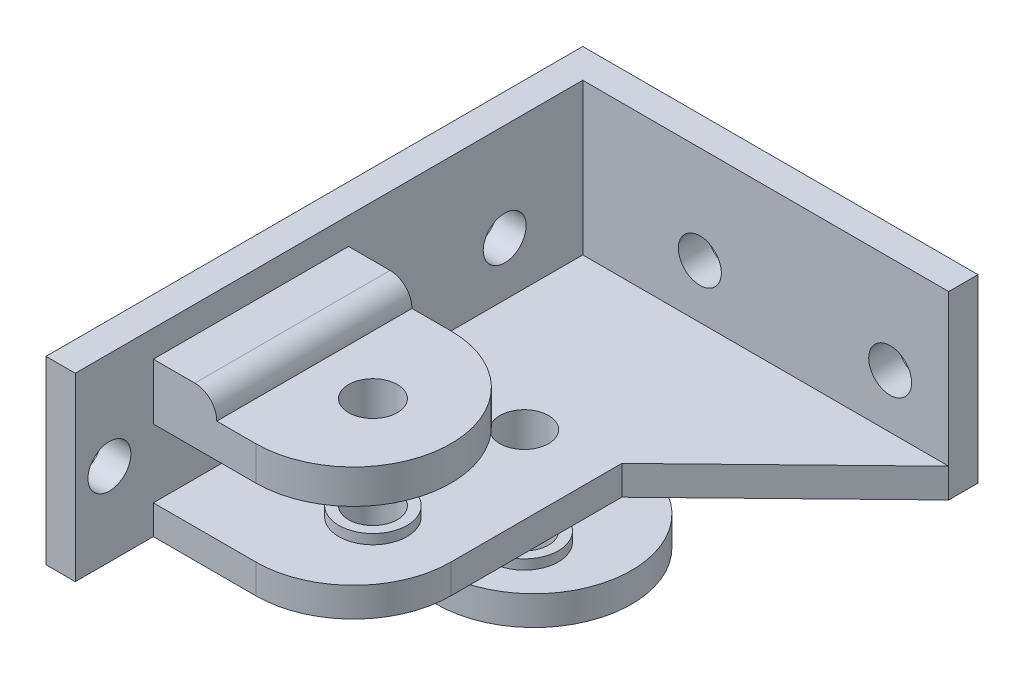
SolidWorks part; units mm, degrees
material "ABS"
ref_plane "Front Plane" through (0, 0, 0) normal (0, 0, 1) x (1, 0, 0)
ref_plane "Top Plane" through (0, 0, 0) normal (0, 1, 0) x (1, 0, 0)
ref_plane "Right Plane" through (0, 0, 0) normal (1, 0, 0) x (0, 0, -1)
sketch "Sketch1" plane through (0, 0, 0) normal (0, 1, 0) x (1, 0, 0)
  line L0 (40.5, 0) -> (0, 0)
  line L1 (0, 0) -> (0, -55)
  line L2 (0, -55) -> (3, -55)
  line L3 (3, -55) -> (3, -3)
  line L4 (3, -3) -> (40.5, -3)
  line L5 (40.5, -3) -> (40.5, 0)
  dimension "D1" = 3
  dimension "D2" = 40.5
  dimension "D3" = 55
extrude "Boss-Extrude1" add sketch "Sketch1" along normal blind 18.5
sketch "Sketch2" plane through (0, 0, 0) normal (0, -1, 0) x (1, 0, 0)
  line L0 (40.5, 3) -> (23.5, 19.5)
  line L1 (23.5, 19.5) -> (23.5, 37)
  line L2 (13.5, 47) -> (3, 47)
  line L3 (3, 3) -> (3, 55) construction
  line L4 (3, 47) -> (3, 3)
  line L5 (3, 3) -> (40.5, 3)
  line L7 (3, 55) -> (0, 55) construction
  line L8 (40.5, 0) -> (0, 0) construction
  arc A0 (13.5, 47) -> (23.5, 37) centre (13.5, 37) cw
  dimension "D3" = 19.5
  dimension "D1" = 10
  dimension "D2" = 17
  dimension "D4" = 8
extrude "Boss-Extrude2" add sketch "Sketch2" against normal blind 3
sketch "Sketch3" plane through (0, 3, 0) normal (0, 1, 0) x (1, 0, 0)
  line L0 (3, -47) -> (13.5, -47)
  line L1 (3, -3) -> (3, -47) construction
  line L2 (13.5, -27) -> (3, -27)
  line L3 (3, -27) -> (3, -47)
  arc A0 (13.5, -27) -> (13.5, -47) centre (13.5, -37) cw
  dimension "D1" = 20
  dimension "D3" = 20.5
extrude "Boss-Extrude3" add sketch "Sketch3" along normal blind 3.5 from offset 7
sketch "Sketch4" plane through (0, 0, 47) normal (0, 0, 1) x (1, 0, 0)
  line L0 (3, 13.5) -> (3, 15.75)
  line L1 (3, 15.75) -> (9.5, 15.75)
  line L2 (9.5, 15.75) -> (9.5, 13.5)
  line L4 (9.5, 13.5) -> (3, 13.5)
  dimension "D1" = 6.5
  dimension "D2" = 2.25
extrude "Boss-Extrude4" add sketch "Sketch4" against normal up to surface (20 mm away) up to face at (8.25, 11.75, 27)
fillet "Fillet1" radius 2.25 1 edges at (9.5, 15.75, 37)
sketch "Sketch5" plane through (0, 0, 0) normal (0, -1, 0) x (1, 0, 0)
  line L0 (0, 28.5) -> (0, 8.5)
  line L1 (0, 55) -> (0, 0) construction
  line L2 (0, 8.5) -> (9, 8.5)
  line L3 (9, 8.5) -> (9, 10.5)
  line L4 (9, 10.5) -> (3, 10.5)
  line L5 (3, 10.5) -> (3, 28.5)
  line L6 (3, 28.5) -> (0, 28.5)
  line L7 (3, 55) -> (0, 55) construction
  line L8 (3, 47) -> (3, 55) construction
  dimension "D1" = 20
  dimension "D2" = 26.5
  dimension "D3" = 2
  dimension "D4" = 9
extrude "Boss-Extrude5" add sketch "Sketch5" along normal blind 7
sketch "Sketch6" plane through (0, -7, 0) normal (0, -1, 0) x (1, 0, 0)
  line L0 (0, 8.5) -> (0, 28.5)
  line L1 (0, 28.5) -> (13.5, 28.5)
  line L2 (13.5, 8.5) -> (0, 8.5)
  arc A0 (13.5, 28.5) -> (13.5, 8.5) centre (13.5, 18.5) cw
  dimension "D1" = 23.5
extrude "Boss-Extrude6" add sketch "Sketch6" along normal blind 3
sketch "Sketch7" plane through (0, 13.5, 0) normal (0, 1, 0) x (1, 0, 0)
  line L2 (0, 0) -> (0, -55) construction
  line L3 (7.25, -47) -> (3, -47) construction
  circle A0 centre (15.5, -21.5) radius 2.5
  circle A1 centre (15.5, -37) radius 2.5
  dimension "D1" = 5
  dimension "D2" = 15.5
  dimension "D3" = 15.5
  dimension "D4" = 10
extrude "Cut-Extrude1" cut sketch "Sketch7" against normal through all
sketch "Sketch8" plane through (0, 0, 0) normal (-1, 0, 0) x (0, 0, 1)
  line L2 (0, 18.5) -> (55, 18.5) construction
  line L3 (0, 18.5) -> (0, 0) construction
  circle A0 centre (11, 8.5) radius 2.2
  circle A1 centre (51.5, 8.5) radius 2.2
  dimension "D1" = 4.4
  dimension "D2" = 40.5
  dimension "D3" = 10
  dimension "D4" = 11
extrude "Cut-Extrude2" cut sketch "Sketch8" against normal through all
sketch "Sketch9" plane through (0, 0, 0) normal (0, 0, -1) x (-1, 0, 0)
  line L2 (-40.5, 18.5) -> (0, 18.5) construction
  line L3 (-40.5, 18.5) -> (-40.5, 0) construction
  circle A0 centre (-34.5, 8.5) radius 2.2
  circle A1 centre (-15, 8.5) radius 2.2
  dimension "D1" = 10
  dimension "D2" = 19.5
  dimension "D3" = 4.4
  dimension "D4" = 6
extrude "Cut-Extrude3" cut sketch "Sketch9" against normal up to next
sketch "Sketch10" plane through (0, -7, 0) normal (0, 1, 0) x (1, 0, 0)
  circle A0 centre (15.5, -21.5) radius 2.5
  circle A1 centre (15.5, -21.5) radius 3.5
  dimension "D1" = 5
  dimension "D2" = 7
extrude "Boss-Extrude7" add sketch "Sketch10" along normal up to next
sketch "Sketch11" plane through (0, 3, 0) normal (0, 1, 0) x (1, 0, 0)
  circle A0 centre (15.5, -37) radius 3.5
  circle A2 centre (15.5, -37) radius 2.5
  dimension "D1" = 7
  dimension "D2" = 5
extrude "Boss-Extrude8" add sketch "Sketch11" along normal up to next
sketch "Sketch12" plane through (0, 0, 47) normal (0, 0, 1) x (1, 0, 0)
  line L0 (19, -7) -> (19, 0) construction
  line L1 (19, -1) -> (12, -1)
  line L2 (19, -1) -> (19, -6)
  line L3 (19, -6) -> (12, -6)
  line L4 (12, -1) -> (12, -6)
  line L5 (12, 0) -> (12, -7) construction
  line L6 (19, 3) -> (19, 10) construction
  line L7 (19, 9) -> (12, 9)
  line L8 (19, 9) -> (19, 4)
  line L9 (19, 4) -> (12, 4)
  line L10 (12, 9) -> (12, 4)
  line L11 (12, 10) -> (12, 3) construction
  line L12 (12, 6.5) -> (19, 6.5) construction
  line L13 (12, -3.5) -> (19, -3.5) construction
  dimension "D1" = 5
  dimension "D2" = 5
extrude "Cut-Extrude4" cut sketch "Sketch12" against normal up to surface (44 mm away) up to face at (12.8, 8.5, 3)
